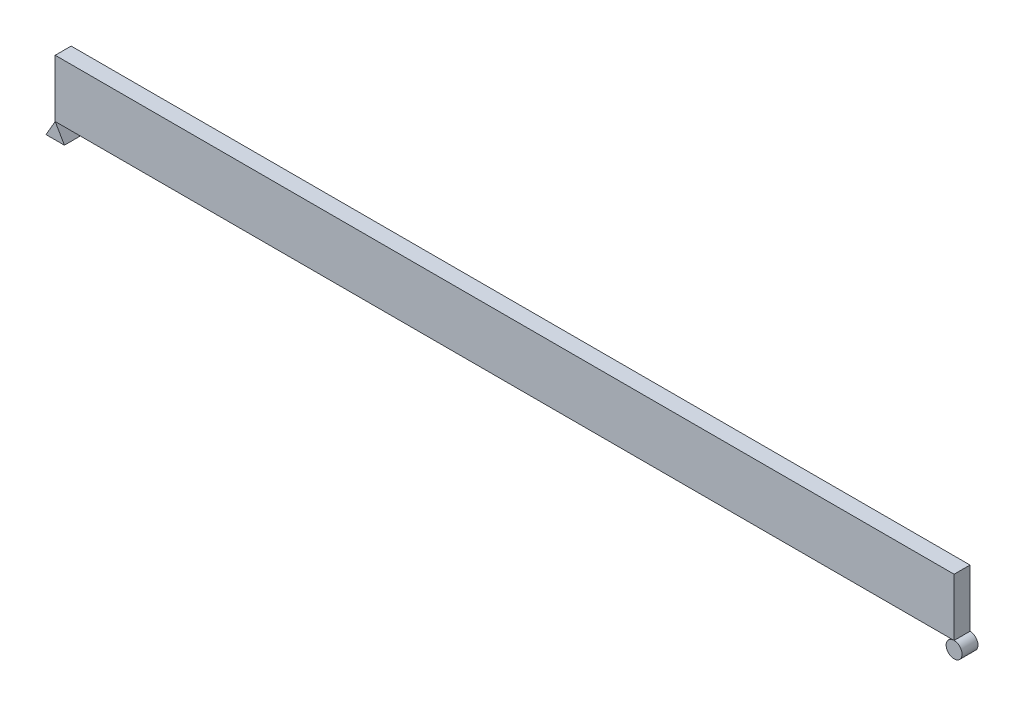
SolidWorks part; units mm, degrees
other "DetailItem1"
other "DetailItem4"
other "DetailItem6"
other "DetailItem7"
other "DetailItem8"
other "DetailItem9"
material "Cast Alloy Steel"
ref_plane "Front Plane" through (0, 0, 0) normal (0, 0, 1) x (1, 0, 0)
ref_plane "Top Plane" through (0, 0, 0) normal (0, 1, 0) x (1, 0, 0)
ref_plane "Right Plane" through (0, 0, 0) normal (1, 0, 0) x (0, 0, -1)
sketch "Sketch1" plane through (0, 0, 0) normal (0, 0, 1) x (1, 0, 0)
  line L1 (-3581.4, 228.6) -> (3581.4, 228.6)
  line L2 (-3581.4, 228.6) -> (-3581.4, -228.6)
  line L3 (-3581.4, -228.6) -> (3581.4, -228.6)
  line L4 (3581.4, 228.6) -> (3581.4, -228.6)
  line L5 (0, -228.6) -> (0, 228.6) construction
  line L6 (-3581.4, 0) -> (3581.4, 0) construction
  line L8 (-3654.7235, -355.6) -> (-3581.4, -228.6)
  line L9 (-3581.4, -228.6) -> (-3508.0765, -355.6)
  line L10 (-3508.0765, -355.6) -> (-3654.7235, -355.6)
  circle A0 centre (3581.4, -292.1) radius 63.5
  point P0 (0, 0)
  dimension "D6" = 127
  dimension "D1" = 457.2
  dimension "D2" = 7162.8
  dimension "D3" = 127
  dimension "D4" = 60
  dimension "D5" = 60
extrude "Boss-Extrude1" add sketch "Sketch1" along normal blind 127 contours L4 L1 L2 L3 | A0 | L9 L10 L8 region at (0, 0, 0)
sketch "Sketch2" plane through (0, 0, 127) normal (0, 0, 1) x (1, 0, 0)
  line L0 (-2667, 648.3464) -> (-2667, 228.6) construction
  line L1 (-3581.4, 228.6) -> (3581.4, 228.6) construction
  line L2 (0, 648.3464) -> (0, 228.6) construction
  line L3 (1905, 648.3464) -> (1905, 228.6) construction
  line L4 (-3581.4, 228.6) -> (-3581.4, -228.6) construction
  line L5 (3581.4, 228.6) -> (3581.4, -228.6) construction
  dimension "D1" = 914.4
  dimension "D2" = 3581.4
  dimension "D3" = 1676.4
sketch3d "3DSketch1"
  line L0 (1905, 228.6, 127) -> (1905, 228.6, 0)
  line L1 (-3581.4, 228.6, 0) -> (3581.4, 228.6, 0) construction
  line L2 (0, 228.6, 127) -> (0, 228.6, 0)
  line L3 (-2667, 228.6, 127) -> (-2667, 228.6, 0)
  line L4 (3581.4, 228.6, 127) -> (3581.4, 228.6, 0) construction
  line L5 (-3581.4, 228.6, 127) -> (-3581.4, 228.6, 0) construction
  point P5 (1905, 228.6, 63.5)
  point P9 (0, 228.6, 63.5)
  point P13 (-2667, 228.6, 63.5)
  point P14 (-2667, 228.6, 63.5)
  point P15 (-2667, 228.6, 63.5)
  dimension "D1" = 1676.4
  dimension "D2" = 3581.4
  dimension "D3" = 914.4
ref_axis "Axis1" through (-2667, 228.6, 63.5) along (0, -1, 0)
ref_axis "Axis2" through (0, 228.6, 63.5) along (0, -1, 0)
ref_axis "Axis3" through (1905, 228.6, 63.5) along (0, -1, 0)
sketch "Sketch3" plane through (0, 0, 0) normal (0, 0, 1) x (1, 0, 0)
  line L0 (-4415.7432, -918.5017) -> (-4345.2112, -924.5545)
  line L1 (-4028.6624, -1107.3914) -> (-4000.9181, -1137.2872)
  line L2 (-4078.7358, -1056.9188) -> (-4106.4802, -1027.023)
  line L3 (-4106.4802, -1027.023) -> (-4143.023, -1167.6698)
  line L4 (-4143.023, -1167.6698) -> (-4000.9181, -1137.2872)
  arc A0 (-4415.7432, -918.5017) -> (-4028.6624, -1107.3914) centre (-4177.3643, -921.0614) cw
  arc A1 (-4345.2112, -924.5545) -> (-4078.7358, -1056.9188) centre (-4177.3643, -921.0614) cw
